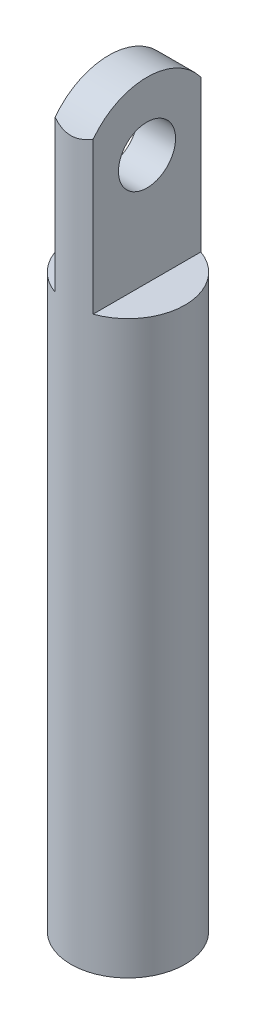
SolidWorks part; units mm, degrees
material "Plain Carbon Steel"
ref_plane "Front Plane" through (0, 0, 0) normal (0, 0, 1) x (1, 0, 0)
ref_plane "Top Plane" through (0, 0, 0) normal (0, 1, 0) x (1, 0, 0)
ref_plane "Right Plane" through (0, 0, 0) normal (1, 0, 0) x (0, 0, -1)
sketch "Sketch1" plane through (0, 0, 0) normal (0, 1, 0) x (1, 0, 0)
  line L2 (1, -2.8284) -> (1, 2.8284)
  line L4 (-1, -2.8284) -> (-1, 2.8284)
  line L5 (0.6771, -2.9226) -> (-0.6771, 2.9226) construction
  line L6 (0.6771, 2.9226) -> (-0.6771, -2.9226) construction
  circle A0 centre (0, 0) radius 3
  dimension "D1" = 6
extrude "Boss-Extrude1" add sketch "Sketch1" against normal blind 30 contours A0
extrude "Boss-Extrude2" add sketch "Sketch1<3>" along normal blind 10 contours L2 A0 L4 region at (0, 0, 0)
sketch "Sketch1<3>" plane through (0, 0, 0) normal (0, 1, 0) x (1, 0, 0) same geometry as "Sketch1"
sketch "Sketch2" plane through (1, 0, 0) normal (1, 0, 0) x (0, 0, -1)
  circle A0 centre (0, 5.8287) radius 1.5
  circle A1 centre (0, 5.8287) radius 3.5
  dimension "D1" = 3
  dimension "D2" = 7
extrude "Cut-Extrude1" cut sketch "Sketch2" against normal blind 10 contours A0
sketch "Sketch3" plane through (1, 0, 0) normal (1, 0, 0) x (0, 0, -1)
  line L0 (3.5417, 5.8287) -> (6.1982, 5.8287)
  line L1 (-4.7986, 5.8287) -> (-3.5417, 5.8287)
  line L2 (-4.7986, 5.8287) -> (-4.7986, 11.427)
  line L3 (-4.7986, 11.427) -> (6.1982, 11.427)
  line L4 (6.1982, 5.8287) -> (6.1982, 11.427)
  arc A0 (3.5417, 5.8287) -> (-3.5417, 5.8287) centre (0, 5.8287) ccw
extrude "Cut-Extrude2" cut sketch "Sketch3" against normal through all both and the other way through all
